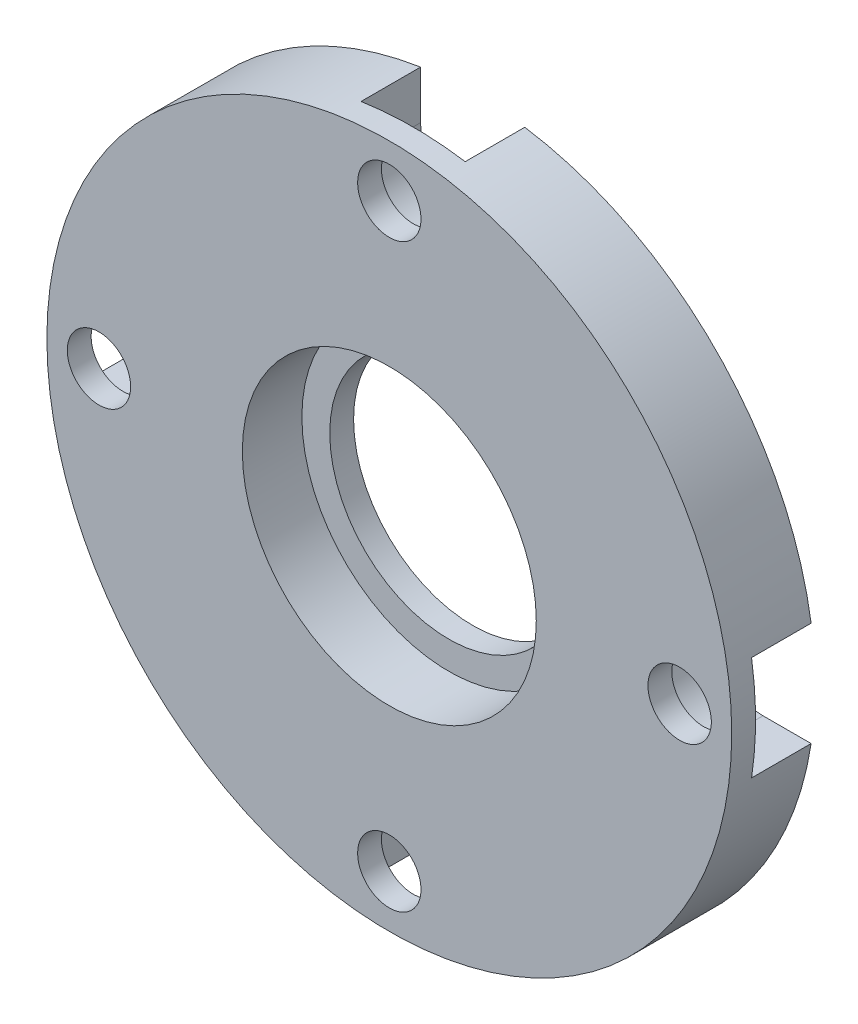
SolidWorks part; units mm, degrees
material "6061-T6 (SS)"
ref_plane "Front Plane" through (0, 0, 0) normal (0, 0, 1) x (1, 0, 0)
ref_plane "Top Plane" through (0, 0, 0) normal (0, 1, 0) x (1, 0, 0)
ref_plane "Right Plane" through (0, 0, 0) normal (1, 0, 0) x (0, 0, -1)
sketch "Derived Main Sketch" plane through (0, 0, 0) normal (1, 0, 0) x (0, 0, -1)
  line L0 (141.5523, 0) -> (-87.5573, 0)
  line L1 (93.1469, 36.5125) -> (0, 36.5125) construction
  line L2 (93.1469, 36.5125) -> (93.1469, -36.5125) construction
  line L3 (93.1469, -36.5125) -> (0, -36.5125) construction
  line L4 (0, 36.5125) -> (0, -36.5125) construction
  line L5 (0, 36.5125) -> (-15.24, 36.5125) construction
  line L6 (0, 36.5125) -> (0, -36.5125) construction
  line L7 (0, -36.5125) -> (-15.24, -36.5125) construction
  line L8 (-15.24, 36.5125) -> (-15.24, -36.5125) construction
  line L9 (-22.86, 9.525) -> (0, 9.525)
  line L10 (-22.86, 9.525) -> (-22.86, -9.525)
  line L11 (-22.86, -9.525) -> (0, -9.525)
  line L12 (0, 9.525) -> (0, -9.525)
  line L13 (22, 10.0076) -> (10, 10.0076)
  line L14 (22, 10.0076) -> (22, -10.0076)
  line L15 (22, -10.0076) -> (10, -10.0076)
  line L16 (10, 10.0076) -> (10, -10.0076)
  line L17 (64.5719, 9.9949) -> (52.5719, 9.9949)
  line L18 (64.5719, 9.9949) -> (64.5719, -9.9949)
  line L19 (64.5719, -9.9949) -> (52.5719, -9.9949)
  line L20 (52.5719, 9.9949) -> (52.5719, -9.9949)
  line L22 (52.5719, 9.9949) -> (22, 9.9949)
  line L23 (52.5719, 9.9949) -> (52.5719, -9.9949)
  line L24 (52.5719, -9.9949) -> (22, -9.9949)
  line L25 (22, 9.9949) -> (22, -9.9949)
  line L26 (64.5719, 9.525) -> (89.9719, 9.525)
  line L27 (64.5719, 9.525) -> (64.5719, -9.525)
  line L28 (64.5719, -9.525) -> (89.9719, -9.525)
  line L29 (89.9719, 9.525) -> (89.9719, -9.525)
  line L30 (115.1417, 7.9375) -> (130.0369, 7.9375)
  line L31 (115.1417, 7.9375) -> (115.1417, -7.9375)
  line L32 (115.1417, -7.9375) -> (130.0369, -7.9375)
  line L33 (130.0369, 7.9375) -> (130.0369, -7.9375)
  line L34 (10, 12.5) -> (0, 12.5)
  line L35 (10, 12.5) -> (10, -12.5)
  line L36 (10, -12.5) -> (0, -12.5)
  line L37 (0, 12.5) -> (0, -12.5)
  line L38 (-41.86, 7.0002) -> (-26.86, 7.0002)
  line L39 (-41.86, 7.0002) -> (-41.86, -7.0002)
  line L40 (-41.86, -7.0002) -> (-26.86, -7.0002)
  line L41 (-26.86, 7.0002) -> (-26.86, -7.0002)
  line L42 (93.1469, 36.5125) -> (102.0369, 36.5125) construction
  line L43 (93.1469, 36.5125) -> (93.1469, -36.5125) construction
  line L44 (93.1469, -36.5125) -> (102.0369, -36.5125) construction
  line L45 (102.0369, 36.5125) -> (102.0369, -36.5125) construction
  line L46 (115.1417, -7.9375) -> (89.9719, -7.9375)
  line L47 (115.1417, -7.9375) -> (115.1417, 7.9375)
  line L48 (115.1417, 7.9375) -> (89.9719, 7.9375)
  line L49 (89.9719, -7.9375) -> (89.9719, 7.9375)
  line L54 (-22.86, 7.5) -> (-26.86, 7.5)
  line L55 (-22.86, 7.5) -> (-22.86, -7.5)
  line L56 (-22.86, -7.5) -> (-26.86, -7.5)
  line L57 (-26.86, 7.5) -> (-26.86, -7.5)
sketch "Cap" plane through (0, 0, 0) normal (1, 0, 0) x (0, 0, -1)
  line L0 (93.1469, 36.5125) -> (93.1469, -36.5125) construction
  line L1 (93.1469, 36.5125) -> (102.0369, 36.5125) construction
  line L2 (102.0369, 36.5125) -> (102.0369, -36.5125) construction
  line L3 (115.1417, 7.9375) -> (89.9719, 7.9375) construction
  line L4 (93.1469, 36.5125) -> (93.1469, -36.5125) construction
  line L5 (93.1469, 36.5125) -> (102.0369, 36.5125) construction
  line L6 (102.0369, 36.5125) -> (102.0369, -36.5125) construction
  line L7 (115.1417, 7.9375) -> (89.9719, 7.9375)
  line L8 (200141.5523, 0) -> (-200087.5573, 0) construction
  line L9 (200141.5523, 0) -> (-200087.5573, 0)
  line L10 (-1000, 0) -> (49000, 0)
  line L11 (102.0369, 12.7) -> (99.4969, 12.7)
  line L12 (99.4969, 12.7) -> (99.4969, 15.6718)
  line L13 (99.4969, 15.6718) -> (93.1469, 15.6718)
  line L14 (93.1469, 15.6718) -> (93.1469, 36.5125) construction
  line L15 (102.0369, 36.5125) -> (102.0369, 12.7) construction
  line L16 (102.0369, 36.5125) -> (93.1469, 36.5125) construction
  line L17 (102.0369, 12.7) -> (102.0369, 36.5125)
  line L18 (102.0369, 36.5125) -> (93.1469, 36.5125)
  line L19 (93.1469, 36.5125) -> (93.1469, 15.6718)
  dimension "D1" = 12.7
  dimension "D2" = 15.6718
  dimension "D3" = 2.54
revolve "Endcap-Revolve" add sketch "Cap" angle 360 about L0
sketch "Bolt Locations" plane through (0, 0, -102.0369) normal (0, 0, -1) x (-1, 0, 0)
  circle A0 centre (0, 0) radius 30.9575 construction
  point P3 (0, 30.9575)
  point P4 (30.9575, 0)
  point P5 (0, -30.9575)
  point P6 (-30.9575, 0)
  dimension "D1" = 61.915
hole_wizard "CBORE for 1/4 Socket Head Cap Screw1" positions "Sketch4" profile "Sketch5" counterbore size "1/4" standard "ANSI Inch" end condition through all
sketch "Sketch4" plane through (0, 0, -102.0369) normal (0, 0, -1) x (-1, 0, 0)
  point P0 (0, 30.9575)
  point P3 (30.9575, 0)
  point P6 (0, -30.9575)
  point P9 (-30.9575, 0)
sketch "Sketch5" plane through (0, 30.9575, -102.0369) normal (1, 0, 0) x (0, 1, 0)
  line L0 (0, 0) -> (0, 8.89)
  line L1 (0, 8.89) -> (3.3782, 8.89)
  line L3 (3.3782, 8.89) -> (3.3782, 6.35)
  line L4 (3.3782, 6.35) -> (5.5562, 6.35)
  line L5 (5.5562, 6.35) -> (5.5562, 0)
  line L7 (5.5562, 0) -> (0, 0)
  line L11 (0, -6.35) -> (0, 107.95) construction
  dimension "Thru Hole Dia." = 6.7564
  dimension "Thru Hole Depth" = 8.89
  dimension "C'Bore Dia." = 11.1125
  dimension "C'Bore Depth" = 6.35
sketch "Bolt-Clearance" plane through (0, 0, -102.0369) normal (0, 0, -1) x (-1, 0, 0)
  line L0 (5.5562, 30.9575) -> (5.5562, 37.3075)
  line L1 (5.5562, 37.3075) -> (-5.5562, 37.3075)
  line L2 (-5.5562, 37.3075) -> (-5.5562, 30.9575)
  line L3 (0, 30.9575) -> (5.5562, 30.9575)
  line L4 (0, 30.9575) -> (-5.5562, 30.9575)
  line L5 (30.9575, 0) -> (30.9575, 5.5562)
  line L6 (37.3075, 5.5562) -> (30.9575, 5.5562)
  line L7 (37.3075, -5.5563) -> (37.3075, 5.5562)
  line L8 (30.9575, -5.5563) -> (37.3075, -5.5563)
  line L9 (30.9575, 0) -> (30.9575, -5.5563)
  line L10 (0, -30.9575) -> (5.5563, -30.9575)
  line L11 (5.5563, -37.3075) -> (5.5563, -30.9575)
  line L12 (-5.5562, -37.3075) -> (5.5563, -37.3075)
  line L13 (-5.5562, -30.9575) -> (-5.5562, -37.3075)
  line L14 (0, -30.9575) -> (-5.5562, -30.9575)
  line L15 (-30.9575, 0) -> (-30.9575, -5.5563)
  line L16 (-37.3075, -5.5563) -> (-30.9575, -5.5563)
  line L17 (-37.3075, 5.5562) -> (-37.3075, -5.5563)
  line L18 (-30.9575, 5.5562) -> (-37.3075, 5.5562)
  line L19 (-30.9575, 0) -> (-30.9575, 5.5562)
  line L20 (0, 0) -> (0, 30.9575) construction
  arc A0 (-0.129, 36.5123) -> (0.129, 36.5123) centre (0, 30.9575) ccw construction
  arc A1 (-0.129, 36.5123) -> (0.129, 36.5123) centre (0, 30.9575) ccw construction
  dimension "D1" = 6.35
  dimension "D3" = 30.9575
  dimension "D2" = 4
extrude "Cut-Extrude1" cut sketch "Bolt-Clearance" against normal up to surface (6.35 mm away) contours L1 L2 L4 L3 L0 | L5 L6 L7 L8 L9 | L10 L11 L12 L13 L14 | L15 L16 L17 L18 L19 up to face at (0, 30.9569, -95.6869)
equation "\"D2@Cap\" = 1.234 / 2"
